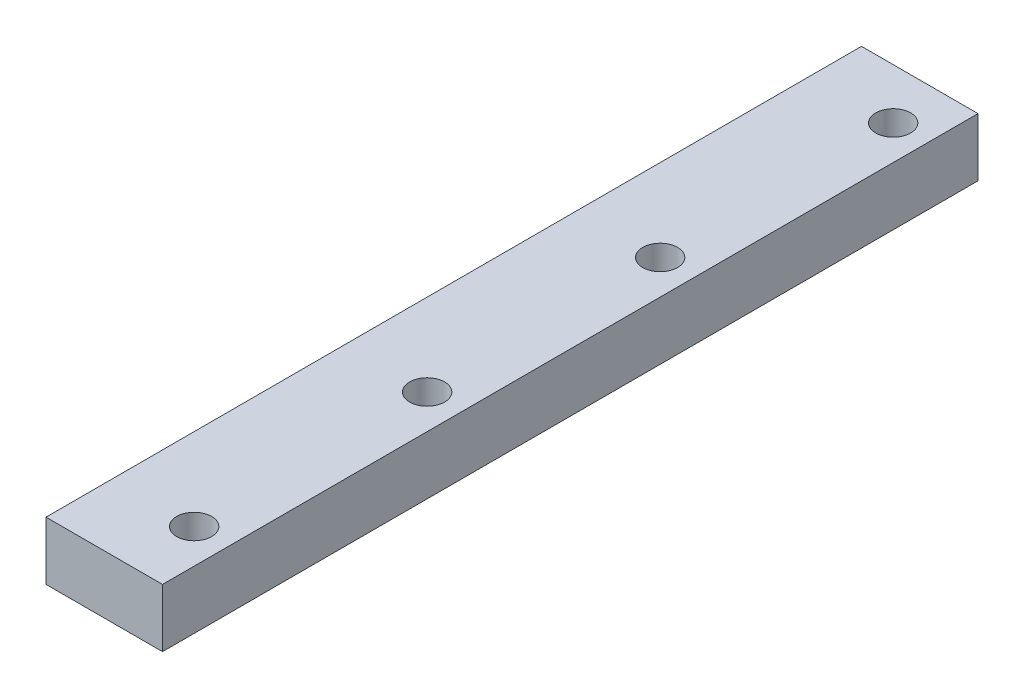
SolidWorks part; units mm, degrees
ref_plane "Front Plane" through (0, 0, 0) normal (0, 0, 1) x (1, 0, 0)
ref_plane "Top Plane" through (0, 0, 0) normal (0, 1, 0) x (1, 0, 0)
ref_plane "Right Plane" through (0, 0, 0) normal (1, 0, 0) x (0, 0, -1)
sketch "Sketch1" plane through (0, 0, 0) normal (0, 0, 1) x (1, 0, 0)
  line L0 (20, 20.188) -> (0, 20.188)
  line L1 (0, 20.188) -> (0, 10.188)
  line L5 (20, 10.188) -> (20, 20.188)
  line L6 (0, 10.188) -> (20, 10.188)
  dimension "D1" = 20
  dimension "D2" = 10
  dimension "D3" = 10
extrude "Boss-Extrude1" add sketch "Sketch1" along normal blind 140
sketch "Sketch2" plane through (0, 20.188, 0) normal (0, 1, 0) x (1, 0, 0)
  circle A0 centre (14.1086, -8.6737) radius 3
  point P2 (14.1086, -8.6737)
extrude "Cut-Extrude1" cut sketch "Sketch2" against normal blind 140
pattern_linear "LPattern1" count 4 spacing 40 along (0, 0, 1) of "Cut-Extrude1"
